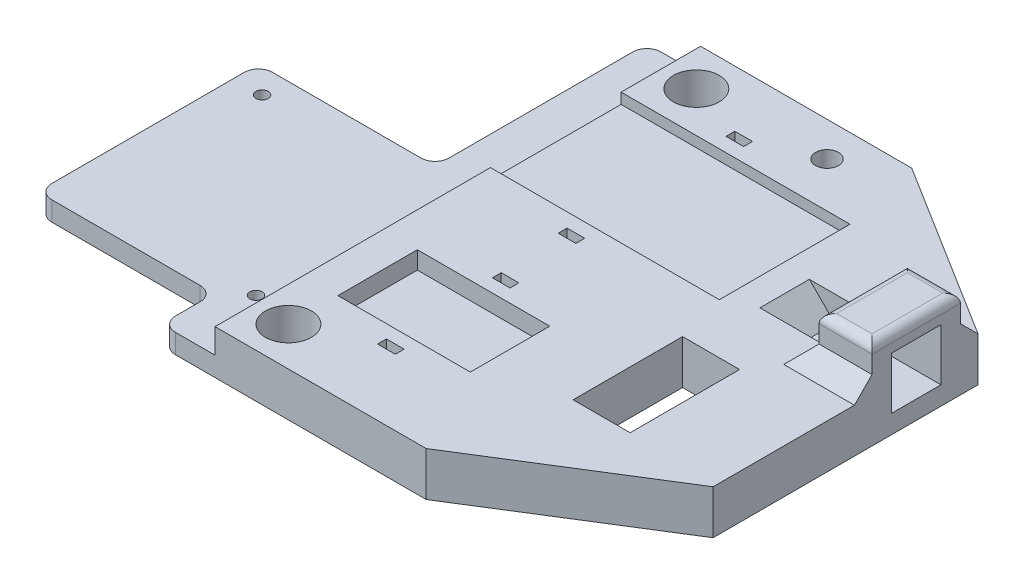
SolidWorks part; units mm, degrees
ref_plane "Front Plane" through (0, 0, 0) normal (0, 0, 1) x (1, 0, 0)
ref_plane "Top Plane" through (0, 0, 0) normal (0, 1, 0) x (1, 0, 0)
ref_plane "Right Plane" through (0, 0, 0) normal (1, 0, 0) x (0, 0, -1)
sketch "Sketch1" plane through (0, 0, 0) normal (0, 1, 0) x (1, 0, 0)
  line L0 (25.4, -5.588) -> (50.8, 10.287)
  line L1 (0, 0) -> (25.4, 0) construction
  line L2 (0, 0) -> (0, 58.674) construction
  line L3 (0, 58.674) -> (25.4, 58.674) construction
  line L4 (25.4, 0) -> (25.4, 58.674) construction
  line L5 (-12.7, 64.262) -> (25.4, 64.262)
  line L6 (-12.7, 64.262) -> (-12.7, -5.588)
  line L7 (-12.7, -5.588) -> (25.4, -5.588)
  line L8 (25.4, 64.262) -> (25.4, -5.588)
  line L9 (25.4, 48.387) -> (50.8, 48.387)
  line L10 (25.4, 48.387) -> (25.4, 10.287)
  line L11 (25.4, 10.287) -> (50.8, 10.287)
  line L12 (50.8, 48.387) -> (50.8, 10.287)
  line L13 (25.4, 64.262) -> (50.8, 48.387)
  line L15 (29.8958, 26.797) -> (38.1, 26.797)
  line L16 (29.8958, 26.797) -> (29.8958, 11.049)
  line L17 (29.8958, 11.049) -> (38.1, 11.049)
  line L18 (38.1, 26.797) -> (38.1, 11.049)
  line L19 (-12.7, 2.032) -> (-38.1, 2.032)
  line L20 (-12.7, 2.032) -> (-12.7, 33.782)
  line L21 (-12.7, 33.782) -> (-38.1, 33.782)
  line L22 (-38.1, 2.032) -> (-38.1, 33.782)
  line L23 (-34.0052, 30.2079) -> (-9.4793, 4.8112) construction
  circle A0 centre (0, 0) radius 3.302
  circle A1 centre (0, 58.674) radius 3.302
  circle A2 centre (18.161, 59.309) radius 1.651
  circle A3 centre (18.161, 59.309) radius 1.651
  circle A4 centre (-21.7423, 17.5095) radius 17.653 construction
  circle A5 centre (-34.0052, 30.2079) radius 0.889
  circle A6 centre (-9.4793, 4.8112) radius 0.889
  point P31 (-32.279, 30.5131)
  point P34 (-21.1705, 17.4537)
  point P35 (-21.7423, 17.5095)
  dimension "D1" = 6.604
  dimension "D3" = 6.604
  dimension "D8" = 3.302
  dimension "D9" = 7.239
  dimension "D19" = 35.306
  dimension "D23" = 1.778
  dimension "D24" = 1.778
  dimension "D2" = 58.674
  dimension "D4" = 25.4
  dimension "D5" = 69.85
  dimension "D6" = 5.588
  dimension "D7" = 38.1
  dimension "D10" = 4.953
  dimension "D12" = 38.1
  dimension "D13" = 15.875
  dimension "D14" = 25.4
  dimension "D15" = 15.748
  dimension "D16" = 8.2042
  dimension "D17" = 21.59
  dimension "D18" = 12.7
  dimension "D20" = 25.4
  dimension "D21" = 30.48
  dimension "D22" = 7.62
  dimension "D11" = 2
extrude "Boss-Extrude1" add sketch "Sketch1" along normal blind 6.35
sketch "Sketch2" plane through (0, 6.35, 0) normal (0, 1, 0) x (1, 0, 0)
  line L6 (-12.7, 64.262) -> (25.4, 64.262) construction
  line L7 (0, 18.542) -> (19.05, 18.542)
  line L8 (0, 18.542) -> (0, 7.112)
  line L9 (0, 7.112) -> (19.05, 7.112)
  line L10 (19.05, 18.542) -> (19.05, 7.112)
  line L12 (25.4, 64.262) -> (25.4, -5.588) construction
  dimension "D1" = 11.43
  dimension "D2" = 19.05
  dimension "D3" = 45.72
  dimension "D4" = 6.35
extrude "Cut-Extrude1" cut sketch "Sketch2" against normal blind 2.54
sketch "Sketch5" plane through (0, 6.35, 0) normal (0, 1, 0) x (1, 0, 0)
  line L0 (19.05, 18.542) -> (0, 18.542) construction
  line L1 (8.89, 20.447) -> (11.43, 20.447)
  line L2 (8.89, 20.447) -> (8.89, 21.717)
  line L3 (8.89, 21.717) -> (11.43, 21.717)
  line L4 (11.43, 20.447) -> (11.43, 21.717)
  line L5 (19.05, 7.112) -> (19.05, 18.542) construction
  line L6 (8.89, 3.937) -> (8.89, 5.207)
  line L7 (8.89, 3.937) -> (11.43, 3.937)
  line L8 (11.43, 3.937) -> (11.43, 5.207)
  line L9 (8.89, 5.207) -> (11.43, 5.207)
  dimension "D1" = 2.54
  dimension "D2" = 1.27
  dimension "D3" = 1.905
  dimension "D4" = 7.62
  dimension "D5" = 2
extrude "Cut-Extrude2" cut sketch "Sketch5" against normal through all both and the other way through all
sketch "Sketch6" plane through (0, 0, 0) normal (0, -1, 0) x (1, 0, 0)
  line L1 (8.89, -5.207) -> (11.43, -5.207)
  line L2 (8.89, -5.207) -> (8.89, -20.447)
  line L3 (8.89, -20.447) -> (11.43, -20.447)
  line L4 (11.43, -5.207) -> (11.43, -20.447)
extrude "Cut-Extrude3" cut sketch "Sketch6" against normal blind 1.016
sketch "Sketch7" plane through (0, 6.35, 0) normal (0, 1, 0) x (1, 0, 0)
  line L1 (-12.7, 52.832) -> (27.94, 52.832)
  line L2 (-12.7, 52.832) -> (-12.7, 34.036)
  line L3 (-12.7, 34.036) -> (27.94, 34.036)
  line L4 (27.94, 52.832) -> (27.94, 34.036)
  line L5 (-12.7, 64.262) -> (-12.7, 33.782) construction
  line L6 (-12.7, 64.262) -> (25.4, 64.262) construction
  line L7 (25.4, 64.262) -> (25.4, -5.588) construction
  dimension "D1" = 18.796
  dimension "D2" = 11.43
  dimension "D3" = 40.64
extrude "Cut-Extrude4" cut sketch "Sketch7" against normal blind 1.524
sketch "Sketch8" plane through (0, 6.35, 0) normal (0, 1, 0) x (1, 0, 0)
  line L0 (27.94, 52.832) -> (-12.7, 52.832) construction
  line L1 (8.0748, 54.864) -> (10.6148, 54.864)
  line L2 (8.0748, 54.864) -> (8.0748, 56.134)
  line L3 (8.0748, 56.134) -> (10.6148, 56.134)
  line L4 (10.6148, 54.864) -> (10.6148, 56.134)
  line L5 (8.0748, 30.734) -> (8.0748, 32.004)
  line L6 (8.0748, 30.734) -> (10.6148, 30.734)
  line L7 (10.6148, 30.734) -> (10.6148, 32.004)
  line L8 (8.0748, 32.004) -> (10.6148, 32.004)
  dimension "D1" = 2.54
  dimension "D2" = 1.27
  dimension "D3" = 2.032
  dimension "D4" = 2
extrude "Cut-Extrude5" cut sketch "Sketch8" against normal through all both and the other way through all
sketch "Sketch10" plane through (0, 0, 0) normal (0, -1, 0) x (1, 0, 0)
  line L1 (8.0748, -32.004) -> (10.6148, -32.004)
  line L2 (8.0748, -32.004) -> (8.0748, -54.864)
  line L3 (8.0748, -54.864) -> (10.6148, -54.864)
  line L4 (10.6148, -32.004) -> (10.6148, -54.864)
extrude "Cut-Extrude6" cut sketch "Sketch10" against normal blind 1.016
sketch "Sketch11" plane through (0, 6.35, 0) normal (0, 1, 0) x (1, 0, 0)
  line L0 (50.8, 48.387) -> (50.8, 10.287) construction
  line L1 (50.8, 45.847) -> (43.18, 45.847)
  line L2 (50.8, 45.847) -> (50.8, 33.147)
  line L3 (50.8, 33.147) -> (43.18, 33.147)
  line L4 (43.18, 45.847) -> (43.18, 33.147)
  dimension "D1" = 12.7
  dimension "D2" = 7.62
  dimension "D3" = 2.54
extrude "Boss-Extrude2" add sketch "Sketch11" along normal blind 6.35
sketch "Sketch13" plane through (50.8, 0, 0) normal (1, 0, 0) x (0, 0, -1)
  line L0 (33.147, 12.7) -> (45.847, 12.7) construction
  line L1 (35.941, 10.16) -> (43.053, 10.16)
  line L2 (35.941, 10.16) -> (35.941, 2.667)
  line L3 (35.941, 2.667) -> (43.053, 2.667)
  line L4 (43.053, 10.16) -> (43.053, 2.667)
  line L5 (33.147, 12.7) -> (33.147, 6.35) construction
  dimension "D1" = 7.112
  dimension "D2" = 7.493
  dimension "D3" = 2.54
  dimension "D4" = 2.794
extrude "Cut-Extrude7" cut sketch "Sketch13" against normal blind 19.05
chamfer "Chamfer3" distance 2.54 angle 45 4 edges at (46.99, 6.35, -45.847) (46.99, 6.35, -33.147) (43.18, 6.35, -44.45) (43.18, 6.35, -34.544)
fillet "Fillet1" radius 1.27 4 edges at (50.8, 12.7, -39.497) (43.18, 12.7, -39.497) (46.99, 12.7, -33.147) (46.99, 12.7, -45.847)
chamfer "Chamfer4" distance 3.81 angle 45 1 edges at (31.75, 2.667, -39.497)
sketch "Sketch14" plane through (0, 6.35, 0) normal (0, 1, 0) x (1, 0, 0)
  line L15 (-12.7, 64.262) -> (25.4, 64.262) construction
  line L16 (-4.9742, 64.262) -> (-38.1, 64.262)
  line L17 (-4.9742, 64.262) -> (-4.9742, -5.588)
  line L18 (-4.9742, -5.588) -> (-38.1, -5.588)
  line L19 (-38.1, 64.262) -> (-38.1, -5.588)
  line L20 (-12.7, -5.588) -> (25.4, -5.588) construction
  line L21 (-38.1, 2.032) -> (-38.1, 33.782) construction
extrude "Cut-Extrude8" cut sketch "Sketch14" against normal blind 3.556
fillet "Fillet2" radius 2.032 6 edges at (-12.7, 1.397, -64.262) (-12.7, 1.397, 5.588) (-12.7, 1.397, -2.032) (-38.1, 1.397, -2.032) (-38.1, 1.397, -33.782) (-12.7, 1.397, -33.782)
sketch "Sketch16" plane through (0, 0, 0) normal (0, -1, 0) x (1, 0, 0)
  line L1 (-10.7493, -7.0109) -> (-8.2093, -7.0109)
  line L2 (-8.2093, -7.0109) -> (-6.9393, -4.8112)
  line L3 (-6.9393, -4.8112) -> (-8.2093, -2.6115)
  line L4 (-8.2093, -2.6115) -> (-10.7493, -2.6115)
  line L5 (-10.7493, -2.6115) -> (-12.0193, -4.8112)
  line L6 (-12.0193, -4.8112) -> (-10.7493, -7.0109)
  line L7 (-32.7499, -32.416) -> (-31.4653, -30.2247)
  line L8 (-31.4653, -30.2247) -> (-32.7207, -28.0167)
  line L9 (-32.7207, -28.0167) -> (-35.2606, -27.9998)
  line L10 (-35.2606, -27.9998) -> (-36.5452, -30.191)
  line L11 (-36.5452, -30.191) -> (-35.2898, -32.3991)
  line L12 (-35.2898, -32.3991) -> (-32.7499, -32.416)
  circle A0 centre (-9.4793, -4.8112) radius 2.1997 construction
  circle A1 centre (-34.0052, -30.2079) radius 2.1997 construction
  dimension "D1" = 2.54
  dimension "D2" = 2.54
extrude "Cut-Extrude9" cut sketch "Sketch16" against normal blind 1.27
